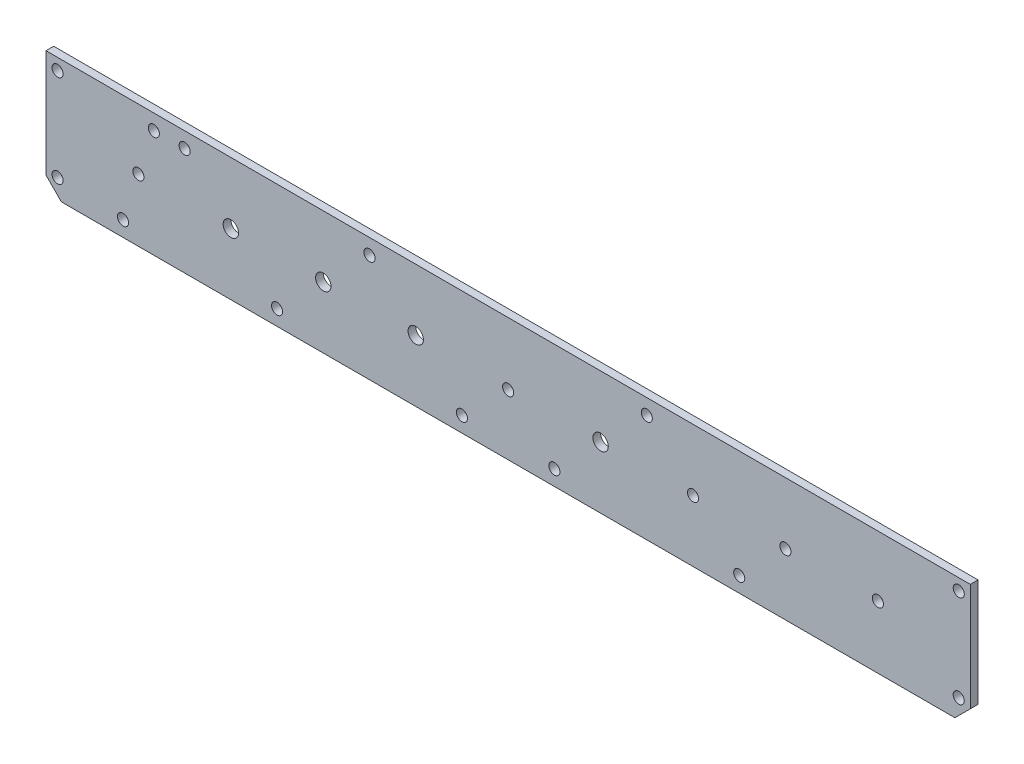
SolidWorks part; units mm, degrees
ref_plane "Front Plane" through (0, 0, 0) normal (0, 0, 1) x (1, 0, 0)
ref_plane "Top Plane" through (0, 0, 0) normal (0, 1, 0) x (1, 0, 0)
ref_plane "Right Plane" through (0, 0, 0) normal (1, 0, 0) x (0, 0, -1)
sketch "Sketch1" plane through (0, 0, 0) normal (0, 0, 1) x (1, 0, 0)
  line L1 (0, 0) -> (381, 0)
  line L2 (0, 0) -> (0, 50.8)
  line L3 (0, 50.8) -> (381, 50.8)
  line L4 (381, 0) -> (381, 50.8)
  dimension "D1" = 50.8
  dimension "D2" = 381
extrude "Boss-Extrude1" add sketch "Sketch1" along normal blind 3.175
sketch "Sketch2" plane through (0, 0, 3.175) normal (0, 0, 1) x (1, 0, 0)
  line L0 (190.5, 25.0031) -> (38.1, 25.7969) construction
  line L1 (190.5, 50.8) -> (190.5, 0) construction
  line L2 (381, 50.8) -> (0, 50.8) construction
  line L3 (0, 0) -> (381, 0) construction
  line L4 (190.5, 25.0031) -> (342.9, 25.7969) construction
  line L5 (0, 6.35) -> (0, 0)
  line L6 (0, 50.8) -> (0, 0) construction
  line L7 (0, 0) -> (6.35, 0)
  line L8 (6.35, 0) -> (0, 6.35)
  line L9 (381, 0) -> (374.65, 0)
  line L10 (374.65, 0) -> (381, 6.35)
  line L11 (381, 6.35) -> (381, 0)
  circle A0 centre (38.1, 25.7969) radius 2.286
  circle A1 centre (190.5, 25.0031) radius 2.286
  circle A2 centre (114.3, 25.4) radius 3.175
  circle A3 centre (76.2, 25.4) radius 3.175
  circle A4 centre (152.4, 25.4) radius 3.175
  circle A5 centre (228.6, 25.4) radius 3.175
  circle A6 centre (304.8, 25.4) radius 2.286
  circle A7 centre (266.7, 25.4) radius 2.286
  circle A8 centre (342.9, 25.7969) radius 2.286
  circle A9 centre (57.15, 44.45) radius 2.286
  circle A10 centre (171.45, 6.35) radius 2.286
  circle A11 centre (209.55, 6.35) radius 2.286
  circle A13 centre (133.35, 44.45) radius 2.286
  circle A14 centre (247.65, 44.45) radius 2.286
  circle A15 centre (95.25, 6.35) radius 2.286
  circle A16 centre (285.75, 6.35) radius 2.286
  circle A17 centre (44.45, 44.45) radius 2.286
  circle A18 centre (31.75, 6.35) radius 2.286
  circle A19 centre (4.7625, 46.0375) radius 2.286
  circle A20 centre (4.7625, 7.9375) radius 2.286
  circle A21 centre (376.2375, 7.9375) radius 2.286
  circle A22 centre (376.2375, 46.0375) radius 2.286
  point P17 (190.5, 25.4)
  point P56 (0, 0)
  dimension "D2" = 4.572
  dimension "D5" = 6.35
  dimension "D7" = 4.572
  dimension "D12" = 4.572
  dimension "D15" = 4.572
  dimension "D16" = 4.572
  dimension "D19" = 4.572
  dimension "D21" = 6.35
  dimension "D27" = 4.572
  dimension "D1" = 0.7937
  dimension "D3" = 38.1
  dimension "D4" = 152.4
  dimension "D6" = 38.1
  dimension "D8" = 57.15
  dimension "D9" = 19.05
  dimension "D10" = 57.15
  dimension "D11" = 19.05
  dimension "D13" = 57.15
  dimension "D14" = 19.05
  dimension "D17" = 19.05
  dimension "D18" = 19.05
  dimension "D20" = 19.05
  dimension "D22" = 6.35
  dimension "D23" = 6.35
  dimension "D24" = 6.35
  dimension "D25" = 4.7625
  dimension "D26" = 4.7625
  dimension "D28" = 7.9375
extrude "Cut-Extrude1" cut sketch "Sketch2" against normal up to next
